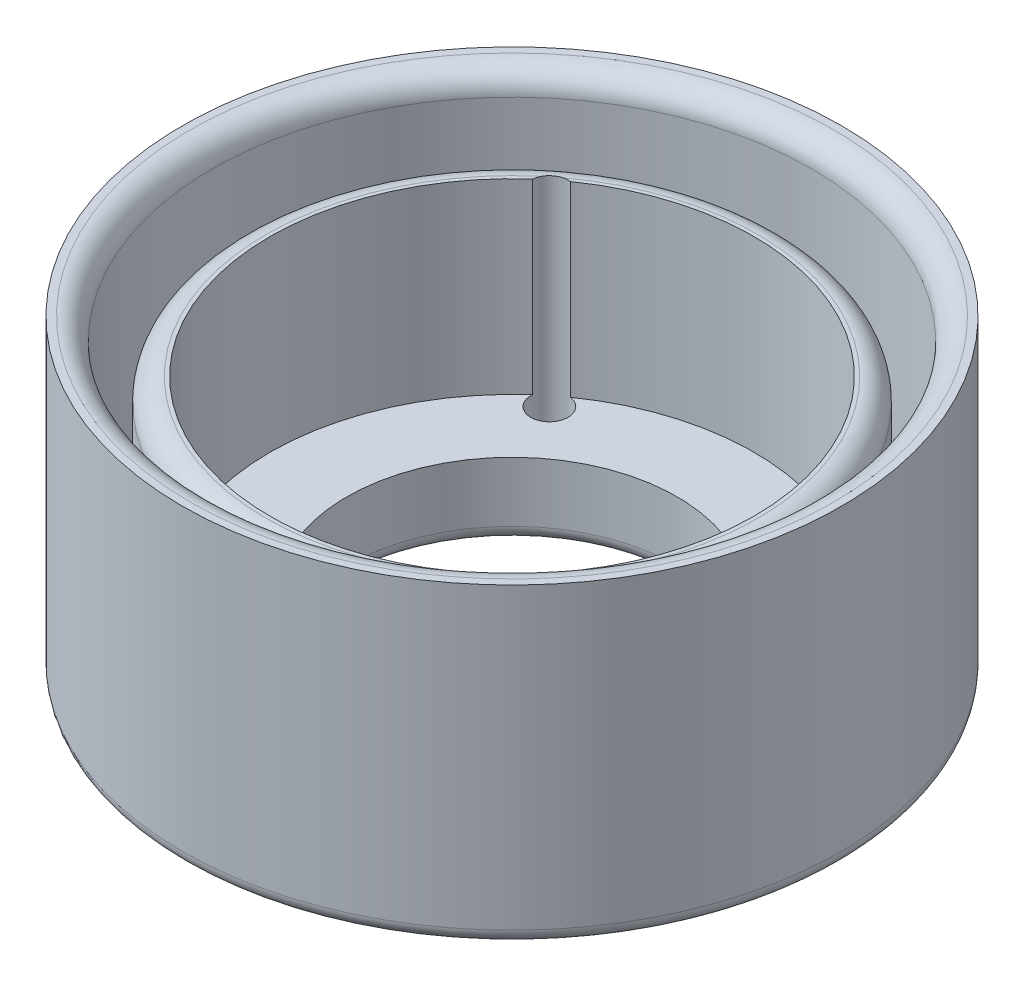
SolidWorks part; units mm, degrees
ref_plane "Alzado" through (0, 0, 0) normal (0, 0, 1) x (1, 0, 0)
ref_plane "Planta" through (0, 0, 0) normal (0, 1, 0) x (1, 0, 0)
ref_plane "Vista lateral" through (0, 0, 0) normal (1, 0, 0) x (0, 0, -1)
sketch "Croquis1" plane through (0, 0, 0) normal (0, 1, 0) x (1, 0, 0)
  circle A0 centre (0, 0) radius 17.95
  circle A1 centre (0, 0) radius 20.05
  circle A2 centre (0, 0) radius 22.05
  circle A3 centre (0, 0) radius 16.2
  dimension "D1" = 35.9
  dimension "D2" = 1.75
  dimension "D3" = 40.1
  dimension "D4" = 2
extrude "Saliente-Extruir1" add sketch "Croquis1" along normal blind 16 contours A2 A1 region at (-21.4263, 0, 0)
extrude "Saliente-Extruir2" add sketch "Croquis1<4>" along normal blind 12.5 separate body contours A0 A3 region at (-17.4423, 0, 0)
sketch "Croquis1<4>" plane through (0, 0, 0) normal (0, 1, 0) x (1, 0, 0) same geometry as "Croquis1"
extrude "Saliente-Extruir4" add sketch "Croquis1<6>" against normal blind 5 contours A3 | A0 A3 | A1 A0 | A2 A1 region at (-17.4423, 0, 0) region at (-19.4829, 0, 0) region at (-21.4263, 0, 0) region at (0, 0, 0)
sketch "Croquis1<6>" plane through (0, 0, 0) normal (0, 1, 0) x (1, 0, 0) same geometry as "Croquis1"
sketch "Croquis4" plane through (0, -5, 0) normal (0, -1, 0) x (1, 0, 0)
  line L0 (9.5, 12) -> (0, 0) construction
  line L1 (0, 0) -> (-9.5, -12) construction
  circle A0 centre (0, 0) radius 11.05
  circle A1 centre (9.5, 12) radius 1.25
  circle A2 centre (-9.5, -12) radius 1.25
  dimension "D1" = 22.1
  dimension "D4" = 2.5
  dimension "D2" = 19
  dimension "D3" = 24
extrude "Cortar-Extruir1" cut sketch "Croquis4" against normal up to next
fillet "Redondeo1" radius 1 1 edges at (0, -5, -11.05)
fillet "Redondeo2" radius 1.5 2 edges at (0, 12.5, 17.95) (0, 16, 20.05)
fillet "Redondeo3" radius 1 1 edges at (0, -5, 22.05)
